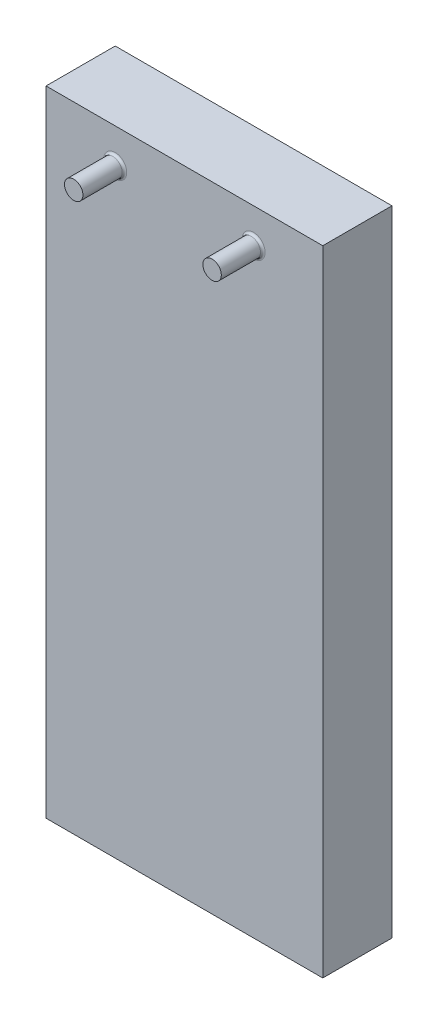
SolidWorks part; units mm, degrees
ref_plane "Front Plane" through (0, 0, 0) normal (0, 0, 1) x (1, 0, 0)
ref_plane "Top Plane" through (0, 0, 0) normal (0, 1, 0) x (1, 0, 0)
ref_plane "Right Plane" through (0, 0, 0) normal (1, 0, 0) x (0, 0, -1)
sketch "Sketch1" plane through (0, 0, 0) normal (0, 1, 0) x (1, 0, 0)
  line L1 (-60, -15) -> (60, -15)
  line L2 (-60, -15) -> (-60, 15)
  line L3 (-60, 15) -> (60, 15)
  line L4 (60, -15) -> (60, 15)
  line L5 (-60, -15) -> (60, 15) construction
  line L6 (-60, 15) -> (60, -15) construction
  point P0 (0, 0)
  dimension "D1" = 120
  dimension "D2" = 30
extrude "Boss-Extrude1" add sketch "Sketch1" along normal blind 275
sketch "Sketch2" plane through (0, 0, 15) normal (0, 0, 1) x (1, 0, 0)
  line L0 (-60, 245) -> (60, 245)
  line L1 (-60, 275) -> (-60, 0) construction
  line L2 (60, 275) -> (60, 0) construction
  line L3 (-60, 275) -> (60, 275) construction
  line L4 (-60, 245) -> (-60, 275)
  line L5 (-60, 260) -> (60, 260) construction
  circle A2 centre (-30, 260) radius 4
  circle A3 centre (30, 260) radius 4
  dimension "D4" = 8
  dimension "D1" = 30
  dimension "D2" = 30
  dimension "D3" = 30
extrude "Boss-Extrude2" add sketch "Sketch2" along normal blind 18 contours L5 A3 | A3 L5 | L5 A2 | A2 L5 region at (-30, 261.6977, 15) region at (30, 261.6977, 15) region at (30, 258.3023, 15) region at (-30, 258.3023, 15)
fillet "Fillet1" radius 1 2 edges at (26, 260, 15) (-34, 260, 15)
equation "\"PCWidth\"= 172mm"
equation "\"PCLength\"= 320mm"
equation "\"PCHeight\"= 242mm"
equation "\"WallThickness\"= 9mm"
equation "\"ThermoBarrierThickness\"= 3mm"
equation "\"HotSideGap\"= 50mm"
equation "\"PCClearance\"= 25mm"
equation "\"RadiatorHeight\"= 275mm"
equation "\"D1@Boss-Extrude1\"=\"RadiatorHeight\""
